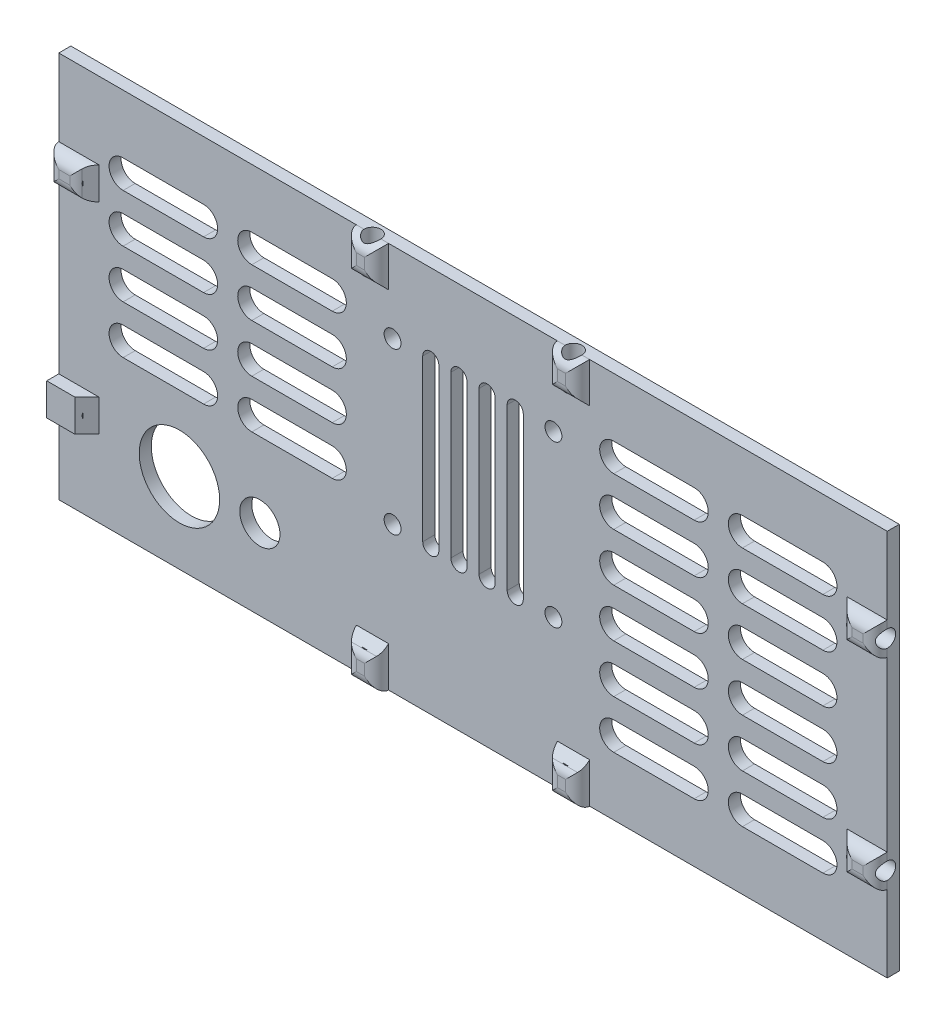
SolidWorks part; units mm, degrees
ref_plane "Front Plane" through (0, 0, 0) normal (1, 0, 0) x (0, 1, 0)
ref_plane "Top Plane" through (0, 0, 0) normal (0, 0, 1) x (0, 1, 0)
ref_plane "Right Plane" through (0, 0, 0) normal (0, 1, 0) x (-1, 0, 0)
sketch "Sketch1" plane through (0, 0, 0) normal (0, 0, 1) x (0, 1, 0)
  line L0 (36.2019, 113.5) -> (76.2019, 113.5) construction
  line L1 (0, 0) -> (96.2019, 0)
  line L2 (0, 0) -> (0, 206)
  line L3 (0, 206) -> (96.2019, 206)
  line L4 (96.2019, 0) -> (96.2019, 206)
  line L5 (36.2019, 115.5) -> (76.2019, 115.5)
  line L6 (36.2019, 111.5) -> (76.2019, 111.5)
  line L7 (36.2019, 106.5) -> (76.2019, 106.5) construction
  line L8 (36.2019, 108.5) -> (76.2019, 108.5)
  line L9 (36.2019, 104.5) -> (76.2019, 104.5)
  line L10 (36.2019, 99.5) -> (76.2019, 99.5) construction
  line L11 (36.2019, 101.5) -> (76.2019, 101.5)
  line L12 (36.2019, 97.5) -> (76.2019, 97.5)
  line L13 (36.2019, 92.5) -> (76.2019, 92.5) construction
  line L14 (36.2019, 94.5) -> (76.2019, 94.5)
  line L15 (36.2019, 90.5) -> (76.2019, 90.5)
  line L16 (6, 200) -> (90.2019, 200) construction
  line L17 (90.2019, 6) -> (90.2019, 200) construction
  line L18 (6, 6) -> (90.2019, 6) construction
  line L19 (6, 6) -> (6, 200) construction
  line L20 (6.101, 68) -> (6.101, 48) construction
  line L21 (9.601, 68) -> (9.601, 48) construction
  line L22 (96.2019, 103) -> (0, 103) construction
  line L23 (2.601, 68) -> (2.601, 48) construction
  line L24 (18.101, 68) -> (18.101, 48) construction
  line L25 (21.601, 68) -> (21.601, 48)
  line L26 (14.601, 68) -> (14.601, 48)
  line L27 (30.1009, 68) -> (30.1009, 48) construction
  line L28 (33.6009, 68) -> (33.601, 48)
  line L29 (26.6009, 68) -> (26.6009, 48)
  line L30 (42.101, 68) -> (42.1009, 48) construction
  line L31 (45.601, 68) -> (45.601, 48)
  line L32 (38.601, 68) -> (38.601, 48)
  line L33 (54.1009, 68) -> (54.1009, 48) construction
  line L34 (57.6009, 68) -> (57.6009, 48)
  line L35 (50.6009, 68) -> (50.6009, 48)
  line L36 (66.1009, 68) -> (66.1009, 48) construction
  line L37 (69.6009, 68) -> (69.6009, 48)
  line L38 (62.6009, 68) -> (62.6009, 48)
  line L39 (78.1009, 68) -> (78.1009, 48) construction
  line L40 (81.6009, 68) -> (81.6009, 48)
  line L41 (74.6009, 68) -> (74.6009, 48)
  line L42 (90.1009, 68) -> (90.1009, 48) construction
  line L43 (93.6009, 68) -> (93.6009, 48) construction
  line L44 (86.6009, 68) -> (86.6009, 48) construction
  line L45 (48.1009, 200) -> (48.1009, 6) construction
  line L46 (6, 42) -> (90.2019, 42) construction
  line L47 (6.101, 16) -> (6.101, 36) construction
  line L48 (9.601, 16) -> (9.601, 36) construction
  line L49 (2.601, 16) -> (2.601, 36) construction
  line L50 (18.101, 16) -> (18.101, 36) construction
  line L51 (21.601, 16) -> (21.601, 36)
  line L52 (14.601, 16) -> (14.601, 36)
  line L53 (30.1009, 16) -> (30.1009, 36) construction
  line L54 (33.6009, 16) -> (33.601, 36)
  line L55 (26.6009, 16) -> (26.6009, 36)
  line L56 (42.101, 16) -> (42.1009, 36) construction
  line L57 (45.601, 16) -> (45.601, 36)
  line L58 (38.601, 16) -> (38.601, 36)
  line L59 (54.1009, 16) -> (54.1009, 36) construction
  line L60 (57.6009, 16) -> (57.6009, 36)
  line L61 (50.6009, 16) -> (50.6009, 36)
  line L62 (66.1009, 16) -> (66.1009, 36) construction
  line L63 (69.6009, 16) -> (69.6009, 36)
  line L64 (62.6009, 16) -> (62.6009, 36)
  line L65 (78.1009, 16) -> (78.1009, 36) construction
  line L66 (81.6009, 16) -> (81.6009, 36)
  line L67 (74.6009, 16) -> (74.6009, 36)
  line L68 (90.1009, 16) -> (90.1009, 36) construction
  line L69 (93.6009, 16) -> (93.6009, 36) construction
  line L70 (86.6009, 16) -> (86.6009, 36) construction
  line L71 (6.101, 138) -> (6.101, 158) construction
  line L72 (9.601, 138) -> (9.601, 158) construction
  line L73 (2.601, 138) -> (2.601, 158) construction
  line L74 (18.101, 138) -> (18.101, 158) construction
  line L75 (21.601, 138) -> (21.601, 158) construction
  line L76 (14.601, 138) -> (14.601, 158) construction
  line L77 (30.1009, 138) -> (30.1009, 158) construction
  line L78 (33.6009, 138) -> (33.601, 158) construction
  line L79 (26.6009, 138) -> (26.6009, 158) construction
  line L80 (42.101, 138) -> (42.1009, 158) construction
  line L81 (45.601, 138) -> (45.601, 158)
  line L82 (38.601, 138) -> (38.601, 158)
  line L83 (54.1009, 138) -> (54.1009, 158) construction
  line L84 (57.6009, 138) -> (57.6009, 158)
  line L85 (50.6009, 138) -> (50.6009, 158)
  line L86 (66.1009, 138) -> (66.1009, 158) construction
  line L87 (69.6009, 138) -> (69.6009, 158)
  line L88 (62.6009, 138) -> (62.6009, 158)
  line L89 (78.1009, 138) -> (78.1009, 158) construction
  line L90 (81.6009, 138) -> (81.6009, 158)
  line L91 (74.6009, 138) -> (74.6009, 158)
  line L92 (90.1009, 138) -> (90.1009, 158) construction
  line L93 (93.6009, 138) -> (93.6009, 158) construction
  line L94 (86.6009, 138) -> (86.6009, 158) construction
  line L95 (6.101, 190) -> (6.101, 170) construction
  line L96 (9.601, 190) -> (9.601, 170) construction
  line L97 (2.601, 190) -> (2.601, 170) construction
  line L98 (18.101, 190) -> (18.101, 170) construction
  line L99 (21.601, 190) -> (21.601, 170) construction
  line L100 (14.601, 190) -> (14.601, 170) construction
  line L101 (30.1009, 190) -> (30.1009, 170) construction
  line L102 (33.6009, 190) -> (33.601, 170) construction
  line L103 (26.6009, 190) -> (26.6009, 170) construction
  line L104 (42.101, 190) -> (42.1009, 170) construction
  line L105 (45.601, 190) -> (45.601, 170)
  line L106 (38.601, 190) -> (38.601, 170)
  line L107 (54.1009, 190) -> (54.1009, 170) construction
  line L108 (57.6009, 190) -> (57.6009, 170)
  line L109 (50.6009, 190) -> (50.6009, 170)
  line L110 (66.1009, 190) -> (66.1009, 170) construction
  line L111 (69.6009, 190) -> (69.6009, 170)
  line L112 (62.6009, 190) -> (62.6009, 170)
  line L113 (78.1009, 190) -> (78.1009, 170) construction
  line L114 (81.6009, 190) -> (81.6009, 170)
  line L115 (74.6009, 190) -> (74.6009, 170)
  line L116 (90.1009, 190) -> (90.1009, 170) construction
  line L117 (93.6009, 190) -> (93.6009, 170) construction
  line L118 (86.6009, 190) -> (86.6009, 170) construction
  arc A0 (36.2019, 115.5) -> (36.2019, 111.5) centre (36.2019, 113.5) ccw
  arc A1 (76.2019, 111.5) -> (76.2019, 115.5) centre (76.2019, 113.5) ccw
  arc A2 (36.2019, 108.5) -> (36.2019, 104.5) centre (36.2019, 106.5) ccw
  arc A3 (76.2019, 104.5) -> (76.2019, 108.5) centre (76.2019, 106.5) ccw
  arc A4 (36.2019, 101.5) -> (36.2019, 97.5) centre (36.2019, 99.5) ccw
  arc A5 (76.2019, 97.5) -> (76.2019, 101.5) centre (76.2019, 99.5) ccw
  arc A6 (36.2019, 94.5) -> (36.2019, 90.5) centre (36.2019, 92.5) ccw
  arc A7 (76.2019, 90.5) -> (76.2019, 94.5) centre (76.2019, 92.5) ccw
  circle A8 centre (36.2019, 123) radius 2.1
  circle A9 centre (76.2019, 123) radius 2.1
  circle A10 centre (36.2019, 83) radius 2.1
  circle A11 centre (76.2019, 83) radius 2.1
  circle A12 centre (20, 176) radius 10
  circle A13 centre (20, 156) radius 5
  arc A14 (9.601, 68) -> (2.601, 68) centre (6.101, 68) ccw construction
  arc A15 (2.601, 48) -> (9.601, 48) centre (6.101, 48) ccw construction
  arc A16 (21.601, 68) -> (14.601, 68) centre (18.101, 68) ccw
  arc A17 (14.601, 48) -> (21.601, 48) centre (18.101, 48) ccw
  arc A18 (33.6009, 68) -> (26.6009, 68) centre (30.1009, 68) ccw
  arc A19 (26.6009, 48) -> (33.601, 48) centre (30.1009, 48) ccw
  arc A20 (45.601, 68) -> (38.601, 68) centre (42.101, 68) ccw
  arc A21 (38.601, 48) -> (45.601, 48) centre (42.1009, 48) ccw
  arc A22 (57.6009, 68) -> (50.6009, 68) centre (54.1009, 68) ccw
  arc A23 (50.6009, 48) -> (57.6009, 48) centre (54.1009, 48) ccw
  arc A24 (69.6009, 68) -> (62.6009, 68) centre (66.1009, 68) ccw
  arc A25 (62.6009, 48) -> (69.6009, 48) centre (66.1009, 48) ccw
  arc A26 (81.6009, 68) -> (74.6009, 68) centre (78.1009, 68) ccw
  arc A27 (74.6009, 48) -> (81.6009, 48) centre (78.1009, 48) ccw
  arc A28 (93.6009, 68) -> (86.6009, 68) centre (90.1009, 68) ccw construction
  arc A29 (86.6009, 48) -> (93.6009, 48) centre (90.1009, 48) ccw construction
  arc A30 (9.601, 16) -> (2.601, 16) centre (6.101, 16) cw construction
  arc A31 (2.601, 36) -> (9.601, 36) centre (6.101, 36) cw construction
  arc A32 (21.601, 16) -> (14.601, 16) centre (18.101, 16) cw
  arc A33 (14.601, 36) -> (21.601, 36) centre (18.101, 36) cw
  arc A34 (33.6009, 16) -> (26.6009, 16) centre (30.1009, 16) cw
  arc A35 (26.6009, 36) -> (33.601, 36) centre (30.1009, 36) cw
  arc A36 (45.601, 16) -> (38.601, 16) centre (42.101, 16) cw
  arc A37 (38.601, 36) -> (45.601, 36) centre (42.1009, 36) cw
  arc A38 (57.6009, 16) -> (50.6009, 16) centre (54.1009, 16) cw
  arc A39 (50.6009, 36) -> (57.6009, 36) centre (54.1009, 36) cw
  arc A40 (69.6009, 16) -> (62.6009, 16) centre (66.1009, 16) cw
  arc A41 (62.6009, 36) -> (69.6009, 36) centre (66.1009, 36) cw
  arc A42 (81.6009, 16) -> (74.6009, 16) centre (78.1009, 16) cw
  arc A43 (74.6009, 36) -> (81.6009, 36) centre (78.1009, 36) cw
  arc A44 (93.6009, 16) -> (86.6009, 16) centre (90.1009, 16) cw construction
  arc A45 (86.6009, 36) -> (93.6009, 36) centre (90.1009, 36) cw construction
  arc A46 (9.601, 138) -> (2.601, 138) centre (6.101, 138) cw construction
  arc A47 (2.601, 158) -> (9.601, 158) centre (6.101, 158) cw construction
  arc A48 (21.601, 138) -> (14.601, 138) centre (18.101, 138) cw construction
  arc A49 (14.601, 158) -> (21.601, 158) centre (18.101, 158) cw construction
  arc A50 (33.6009, 138) -> (26.6009, 138) centre (30.1009, 138) cw construction
  arc A51 (26.6009, 158) -> (33.601, 158) centre (30.1009, 158) cw construction
  arc A52 (45.601, 138) -> (38.601, 138) centre (42.101, 138) cw
  arc A53 (38.601, 158) -> (45.601, 158) centre (42.1009, 158) cw
  arc A54 (57.6009, 138) -> (50.6009, 138) centre (54.1009, 138) cw
  arc A55 (50.6009, 158) -> (57.6009, 158) centre (54.1009, 158) cw
  arc A56 (69.6009, 138) -> (62.6009, 138) centre (66.1009, 138) cw
  arc A57 (62.6009, 158) -> (69.6009, 158) centre (66.1009, 158) cw
  arc A58 (81.6009, 138) -> (74.6009, 138) centre (78.1009, 138) cw
  arc A59 (74.6009, 158) -> (81.6009, 158) centre (78.1009, 158) cw
  arc A60 (93.6009, 138) -> (86.6009, 138) centre (90.1009, 138) cw construction
  arc A61 (86.6009, 158) -> (93.6009, 158) centre (90.1009, 158) cw construction
  arc A62 (9.601, 190) -> (2.601, 190) centre (6.101, 190) ccw construction
  arc A63 (2.601, 170) -> (9.601, 170) centre (6.101, 170) ccw construction
  arc A64 (21.601, 190) -> (14.601, 190) centre (18.101, 190) ccw construction
  arc A65 (14.601, 170) -> (21.601, 170) centre (18.101, 170) ccw construction
  arc A66 (33.6009, 190) -> (26.6009, 190) centre (30.1009, 190) ccw construction
  arc A67 (26.6009, 170) -> (33.601, 170) centre (30.1009, 170) ccw construction
  arc A68 (45.601, 190) -> (38.601, 190) centre (42.101, 190) ccw
  arc A69 (38.601, 170) -> (45.601, 170) centre (42.1009, 170) ccw
  arc A70 (57.6009, 190) -> (50.6009, 190) centre (54.1009, 190) ccw
  arc A71 (50.6009, 170) -> (57.6009, 170) centre (54.1009, 170) ccw
  arc A72 (69.6009, 190) -> (62.6009, 190) centre (66.1009, 190) ccw
  arc A73 (62.6009, 170) -> (69.6009, 170) centre (66.1009, 170) ccw
  arc A74 (81.6009, 190) -> (74.6009, 190) centre (78.1009, 190) ccw
  arc A75 (74.6009, 170) -> (81.6009, 170) centre (78.1009, 170) ccw
  arc A76 (93.6009, 190) -> (86.6009, 190) centre (90.1009, 190) ccw construction
  arc A77 (86.6009, 170) -> (93.6009, 170) centre (90.1009, 170) ccw construction
  point P7 (56.2019, 113.5)
  point P12 (56.2019, 106.5)
  point P19 (56.2019, 99.5)
  point P26 (56.2019, 92.5)
  point P39 (6.101, 58)
  point P40 (90.1952, 103)
  point P57 (18.101, 58)
  point P65 (30.1009, 58)
  point P72 (42.101, 58)
  point P81 (54.1009, 58)
  point P88 (66.1009, 58)
  point P95 (78.1009, 58)
  point P102 (90.1009, 58)
  point P116 (6.101, 26)
  point P123 (18.101, 26)
  point P130 (30.1009, 26)
  point P137 (42.101, 26)
  point P144 (54.1009, 26)
  point P151 (66.1009, 26)
  point P158 (78.1009, 26)
  point P165 (90.1009, 26)
  point P172 (6.101, 148)
  point P179 (18.101, 148)
  point P186 (30.1009, 148)
  point P193 (42.101, 148)
  point P200 (54.1009, 148)
  point P207 (66.1009, 148)
  point P214 (78.1009, 148)
  point P221 (90.1009, 148)
  point P228 (6.101, 180)
  point P235 (18.101, 180)
  point P242 (30.1009, 180)
  point P249 (42.101, 180)
  point P256 (54.1009, 180)
  point P263 (66.1009, 180)
  point P270 (78.1009, 180)
  point P277 (90.1009, 180)
  dimension "D9" = 4.2
  dimension "D13" = 20
  dimension "D14" = 10
  dimension "D1" = 96.2019
  dimension "D2" = 206
  dimension "D5" = 3
  dimension "D7" = 4
  dimension "D11" = 20
  dimension "D12" = 40
  dimension "D10" = 40
  dimension "D6" = 3
  dimension "D15" = 20
  dimension "D16" = 30
  dimension "D17" = 20
  dimension "D19" = 7
  dimension "D20" = 20
  dimension "D21" = 5
  dimension "D22" = 6
  dimension "D23" = 10
  dimension "D3" = 6
  dimension "D18" = 8
extrude "Boss-Extrude1" add sketch "Sketch1" along normal blind 3
sketch "Sketch2" plane through (0, 0, 0) normal (0, -1, 0) x (1, 0, 0)
  line L0 (-128, 6) -> (-128, 0) construction
  line L1 (-132, 6) -> (-124, 6)
  line L2 (-132, 6) -> (-132, 0)
  line L3 (-132, 6) -> (-132, 0)
  line L4 (-124, 6) -> (-124, 0)
  line L5 (-103, 3) -> (-103, 0) construction
  line L6 (-206, 3) -> (0, 3) construction
  line L7 (-206, 0) -> (0, 0) construction
  line L8 (-132, 0) -> (-124, 0)
  line L9 (-124, 6) -> (-124, 0)
  line L10 (-78, 6) -> (-78, 0) construction
  line L11 (-82, 6) -> (-82, 0)
  line L12 (-74, 0) -> (-82, 0)
  line L13 (-82, 6) -> (-82, 0)
  line L14 (-74, 6) -> (-74, 0)
  line L15 (-74, 6) -> (-74, 0)
  line L16 (-74, 6) -> (-82, 6)
  circle A0 centre (-128, 3) radius 2.1
  circle A2 centre (-78, 3) radius 2.1
  line M3 (-206, 0) -> (0, 0)
  line M5 (0, 3) -> (-206, 3)
  dimension "D3" = 6
  dimension "D1" = 4.2
  dimension "D4" = 25
extrude "Boss-Extrude6" add sketch "Sketch2<4>" against normal blind 10 contours A2 L14 L16 L11 M5 | A2 L11 L14 M5 M3 | A2 M5 | A2 M5 | A0 L4 L1 L2 M5 | A0 L2 L4 M5 M3 | A0 M5 | A0 M5 region at (-128, 0, 5.9146) region at (-131.05, 0, 2.9146) region at (-128, 0, 2.1087) region at (-128, 0, 3.8913) region at (-81.05, 0, 2.9146) region at (-81.9146, 0, 4.5) region at (-78, 0, 2.1087) region at (-78, 0, 3.8913)
sketch "Sketch2<4>" plane through (0, 0, 0) normal (0, -1, 0) x (1, 0, 0) same geometry as "Sketch2"
extrude "Boss-Extrude7" add sketch "Sketch2" along normal blind 10 from surface contours A0 L4 L1 L2 M5 | A0 L2 L4 M5 M3 | A0 M5 | A0 M5 | A2 L11 L14 M5 M3 | A2 M5 | A2 L14 L16 L11 M5 | A2 M5 region at (-128, 0, 5.9146) region at (-131.05, 0, 2.9146) region at (-128, 0, 2.1087) region at (-128, 0, 3.8913) region at (-81.05, 0, 2.9146) region at (-81.9146, 0, 4.5) region at (-78, 0, 2.1087) region at (-78, 0, 3.8913) starting at face at (-103, 96.2019, 1.5)
sketch "Sketch3" plane through (0, 0, 0) normal (1, 0, 0) x (0, 1, 0)
  line L1 (23.1009, 6) -> (23.1009, 0) construction
  line L4 (0, 3) -> (96.2019, 3) construction
  line L5 (48.1009, 3) -> (48.1009, 0) construction
  line L6 (0, 0) -> (96.2019, 0) construction
  line L7 (19.1009, 6) -> (27.1009, 6)
  line L8 (19.1009, 6) -> (19.1009, 0)
  line L9 (19.1009, 0) -> (27.1009, 0)
  line L10 (27.1009, 6) -> (27.1009, 0)
  line L11 (19.1009, 6) -> (19.1009, 0)
  line L12 (27.1009, 6) -> (27.1009, 0)
  line L13 (19.1009, 6) -> (19.1009, 0)
  line L14 (27.1009, 6) -> (27.1009, 0)
  line L15 (19.1009, 6) -> (19.1009, 0)
  line L16 (27.1009, 6) -> (27.1009, 0)
  line L17 (69.1009, 6) -> (69.1009, 0)
  line L18 (77.1009, 0) -> (69.1009, 0)
  line L19 (77.1009, 6) -> (77.1009, 0)
  line L20 (77.1009, 6) -> (69.1009, 6)
  circle A0 centre (23.1009, 3) radius 2.1
  circle A2 centre (73.1009, 3) radius 2.1
  line M3 (0, 0) -> (96.2019, 0)
  line M5 (96.2019, 3) -> (0, 3)
  dimension "D1" = 4.2
  dimension "D4" = 25
  dimension "D2" = 6
  dimension "D3" = 8
extrude "Boss-Extrude3" add sketch "Sketch3<3>" against normal blind 10 contours A2 L19 L20 L17 M5 | A2 L17 L19 M5 M3 | A2 M5 | A2 M5 | A0 L10 L7 L8 M5 | A0 L8 L10 M5 M3 | A0 M5 | A0 M5 region at (0, 23.1009, 5.9146) region at (0, 20.051, 2.9146) region at (0, 23.1009, 2.1087) region at (0, 23.1009, 3.8913) region at (0, 70.051, 2.9146) region at (0, 69.1864, 4.5) region at (0, 73.1009, 2.1087) region at (0, 73.1009, 3.8913)
sketch "Sketch3<3>" plane through (0, 0, 0) normal (1, 0, 0) x (0, 1, 0) same geometry as "Sketch3"
extrude "Boss-Extrude4" add sketch "Sketch3" along normal blind 10 from surface contours A0 L10 L7 L8 M5 | A0 L8 L10 M5 M3 | A0 M5 | A0 M5 | A2 L19 L20 L17 M5 | A2 L17 L19 M5 M3 | A2 M5 | A2 M5 region at (0, 23.1009, 5.9146) region at (0, 20.051, 2.9146) region at (0, 23.1009, 2.1087) region at (0, 23.1009, 3.8913) region at (0, 70.051, 2.9146) region at (0, 69.1864, 4.5) region at (0, 73.1009, 2.1087) region at (0, 73.1009, 3.8913) starting at face at (-206, 48.1009, 1.5)
extrude "Cut-Extrude4" cut sketch "Sketch3<2>" along normal blind 8 from surface contours A0 M5 | A0 M5 | A2 M5 | A2 M5 region at (0, 23.1009, 2.1087) region at (0, 23.1009, 3.8913) region at (0, 73.1009, 2.1087) region at (0, 73.1009, 3.8913) starting at face at (-206, 48.1009, 3.5)
sketch "Sketch3<2>" plane through (0, 0, 0) normal (1, 0, 0) x (0, 1, 0) same geometry as "Sketch3"
extrude "Cut-Extrude5" cut sketch "Sketch3<5>" against normal blind 8 contours A0 M5 | A0 M5 | A2 M5 | A2 M5 region at (0, 23.1009, 2.1087) region at (0, 23.1009, 3.8913) region at (0, 73.1009, 2.1087) region at (0, 73.1009, 3.8913)
sketch "Sketch3<5>" plane through (0, 0, 0) normal (1, 0, 0) x (0, 1, 0) same geometry as "Sketch3"
extrude "Cut-Extrude6" cut sketch "Sketch2<6>" against normal blind 8 contours A2 M5 | A2 M5 | A0 M5 | A0 M5 region at (-128, 0, 2.1087) region at (-128, 0, 3.8913) region at (-78, 0, 2.1087) region at (-78, 0, 3.8913)
sketch "Sketch2<6>" plane through (0, 0, 0) normal (0, -1, 0) x (1, 0, 0) same geometry as "Sketch2"
extrude "Cut-Extrude7" cut sketch "Sketch2<7>" along normal blind 8 from surface contours A2 M5 | A2 M5 | A0 M5 | A0 M5 region at (-128, 0, 2.1087) region at (-128, 0, 3.8913) region at (-78, 0, 2.1087) region at (-78, 0, 3.8913) starting at face at (-103, 96.2019, 3.5)
sketch "Sketch2<7>" plane through (0, 0, 0) normal (0, -1, 0) x (1, 0, 0) same geometry as "Sketch2"
chamfer "Chamfer1" distance 3 angle 45 8 edges at (-78, 86.2019, 6) (-78, 10, 6) (-128, 10, 6) (-128, 86.2019, 6) (-10, 73.1009, 6) (-10, 23.1009, 6) (-196, 73.1009, 6) (-196, 23.1009, 6)
fillet "Fillet1" radius 3 28 edges at (-78, 96.2019, 6) (-74, 92.7019, 6) (-78, 89.2019, 6) (-82, 92.7019, 6) (-128, 96.2019, 6) (-124, 92.7019, 6) (-128, 89.2019, 6) (-132, 92.7019, 6) (-206, 73.1009, 6) (-202.5, 77.1009, 6) (-199, 73.1009, 6) (-202.5, 69.1009, 6) (-128, 0, 6) (-132, 3.5, 6) (-128, 7, 6) (-124, 3.5, 6) (-78, 0, 6) (-82, 3.5, 6) (-78, 7, 6) (-74, 3.5, 6) (0, 73.1009, 6) (-3.5, 69.1009, 6) (-7, 73.1009, 6) (-3.5, 77.1009, 6) (0, 23.1009, 6) (-3.5, 19.1009, 6) (-7, 23.1009, 6) (-3.5, 27.1009, 6)
equation "\"MotorDriverLength\"= 60mm"
equation "\"MotorLength\"= 60"
equation "\"MotorDriverWidth\"=44"
equation "\"MotorWidth\"= 37"
equation "\"InnerWallThickness\"=3"
equation "\"BatteryWidth\"= 60"
equation "\"OuterWallThickness\" = 6"
equation "\"CompartmentHeight\"=37"
equation "\"CompartmentWidth\"= \"MotorDriverLength\""
equation "\"MotorDiameter\"=37"
equation "\"BatteryHeight\"=24.2019"
equation "\"MotorDriverHeight\"=28"
equation "\"CircuitHeight\"=30"
equation "\"FanThickness\"= 10"
equation "\"FanHeight\"=50"
equation "\"MotorShaftHole\"=12"
equation "\"BearingBore\"=4"
equation "\"MinShinWidth\"= 20"
equation "\"ShinThickness\"=10"
equation "\"PivotDistance\"=30"
equation "\"ThighLength\"= 200"
equation "\"KneeLength\" =20"
equation "\"HipBore\"=27"
equation "\"ThighThickness\"=20"
equation "\"MaxBending\"=135"
equation "\"MaxStretchingAngle\"= 140"
equation "\"ThighJointDistance\"=157.485"
equation "\"ShinLength\"=120"
equation "\"BearingDiameter\"= 10"
equation "\"CircuitLength\"=50"
equation "\"ChessisInnerWidth\"= \"OuterWallThickness\" * 2 + \"MotorDriverLength\" + \"MotorDiameter\" + \"InnerWallThickness\" * 3 + \"CircuitLength\""
equation "\"ChessisHeight\"= \"BatteryHeight\" + 10 + \"InnerWallThickness\" + \"MotorDiameter\" + 10 + \"OuterWallThickness\" * 2"
equation "\"D1@Sketch1\"=\"ChessisHeight\""
equation "\"ChassisWidth\"= \"MotorDriverWidth\"*4+30"
equation "\"D2@Sketch1\"=\"ChassisWidth\""
equation "\"D1@Boss-Extrude1\"=3"
equation "\"D3@Sketch2\"=\"OuterWallThickness\""
equation "\"D2@Sketch3\"=\"OuterWallThickness\""
